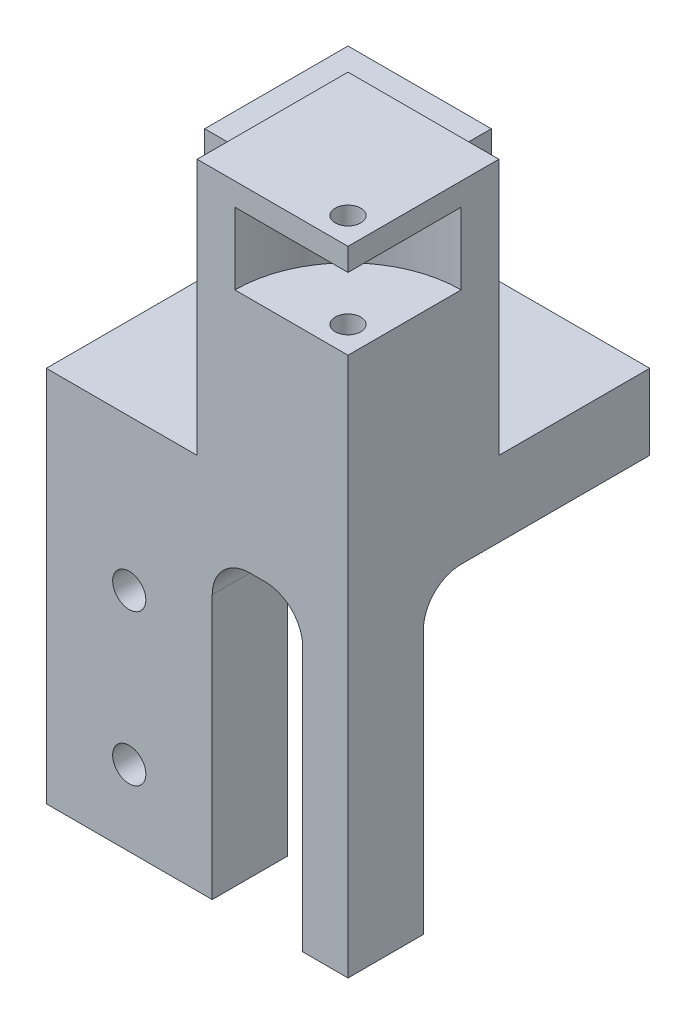
SolidWorks part; units mm, degrees
ref_plane "Front Plane" through (0, 0, 0) normal (0, 0, 1) x (1, 0, 0)
ref_plane "Top Plane" through (0, 0, 0) normal (0, 1, 0) x (1, 0, 0)
ref_plane "Right Plane" through (0, 0, 0) normal (1, 0, 0) x (0, 0, -1)
sketch "Sketch1" plane through (0, 0, 0) normal (0, 0, 1) x (1, 0, 0)
  line L0 (22, 0) -> (-22, 0) construction
  line L1 (-6.3654, 0) -> (33.6346, 0)
  line L2 (-6.3654, 0) -> (-6.3654, -50)
  line L3 (-6.3654, -50) -> (33.6346, -50)
  line L4 (33.6346, 0) -> (33.6346, -50)
  line L5 (13.6346, -50) -> (13.6346, 0) construction
  line L6 (-6.3654, -25) -> (33.6346, -25) construction
  point P252 (13.6346, -25)
  dimension "D1" = 50
  dimension "D2" = 40
extrude "Boss-Extrude1" add sketch "Sketch1" along normal blind 10
sketch "Sketch2" plane through (0, 0, 0) normal (0, 0, 1) x (1, 0, 0)
  line L0 (33.6346, 0) -> (-6.3654, 0) construction
  line L1 (33.6346, 0) -> (-6.3654, 0)
  line L2 (33.6346, 0) -> (33.6346, -10)
  line L3 (33.6346, -10) -> (-6.3654, -10)
  line L4 (-6.3654, 0) -> (-6.3654, -10)
  line L5 (13.6346, -10) -> (13.6346, 0) construction
  line L6 (33.6346, -5) -> (-6.3654, -5) construction
  line L7 (-6.3654, 0) -> (-6.3654, -50) construction
  line L8 (33.6346, -50) -> (33.6346, 0) construction
  point P164 (13.6346, -5)
  dimension "D1" = 10
extrude "Boss-Extrude2" add sketch "Sketch2" against normal blind 30
sketch "Sketch3" plane through (0, 0, 0) normal (0, 1, 0) x (1, 0, 0)
  line L0 (33.6346, -10) -> (33.6346, 30) construction
  line L1 (33.6346, -10) -> (13.6346, -10)
  line L2 (33.6346, -10) -> (33.6346, 10)
  line L3 (33.6346, 10) -> (13.6346, 10)
  line L4 (13.6346, -10) -> (13.6346, 10)
  line L9 (33.6346, -10) -> (-6.3654, -10) construction
  dimension "D1" = 20
  dimension "D2" = 20
extrude "Boss-Extrude3" add sketch "Sketch3" along normal blind 34
sketch "Sketch4" plane through (0, 0, 0) normal (0, 1, 0) x (1, 0, 0)
  line L0 (-974.1415, 10) -> (49025.8585, 10) construction
  line L1 (33.6346, 10) -> (13.6346, 10) construction
  line L8 (-6.3654, 30) -> (12.6346, 30)
  line L14 (-6.3654, 30) -> (-6.3654, 11)
  line L15 (-6.3654, 11) -> (12.6346, 11)
  line L16 (12.6346, 30) -> (12.6346, 11)
  line L17 (3.1346, 11) -> (3.1346, 30) construction
  line L18 (-6.3654, 20.5) -> (12.6346, 20.5) construction
  point P5 (23.6346, 10)
  point P165 (3.1346, 20.5)
  dimension "D1" = 19
  dimension "D2" = 19
  dimension "D3" = 19
extrude "Boss-Extrude4" add sketch "Sketch4" along normal blind 17
ref_plane "Plane2" through (0, 31, 0) normal (0, 1, 0) x (1, 0, 0)
sketch "Sketch6" plane through (0, 31, 0) normal (0, 1, 0) x (1, 0, 0)
  line L1 (13.6346, -10) -> (33.6346, -10) construction
  line L2 (33.6346, -10) -> (33.6346, 10) construction
  line L3 (33.6346, 5) -> (33.6346, -10)
  line L4 (33.6346, -10) -> (18.6346, -10)
  arc A1 (18.6346, -10) -> (33.6346, 5) centre (33.6346, -10) cw
  dimension "D1" = 15
extrude "Cut-Extrude4" cut sketch "Sketch6" against normal blind 9.5
ref_plane "Plane3" through (0, 15, 0) normal (0, 1, 0) x (1, 0, 0)
sketch "Sketch7" plane through (0, 15, 0) normal (0, 1, 0) x (1, 0, 0)
  line L0 (-2.3654, 11) -> (12.6346, 11)
  line L1 (12.6346, 11) -> (12.6346, 26)
  line L6 (12.6346, 11) -> (12.6346, 30) construction
  line L9 (-6.3654, 11) -> (12.6346, 11) construction
  arc A2 (-2.3654, 11) -> (12.6346, 26) centre (12.6346, 11) cw
  dimension "D2" = 15
extrude "Cut-Extrude13" cut sketch "Sketch7" against normal blind 9.5
sketch "Sketch8" plane through (0, 17, 0) normal (0, 1, 0) x (1, 0, 0)
  line L0 (-6.3654, 11) -> (12.6346, 11) construction
  line L1 (-6.3654, 30) -> (12.6346, 30)
  line L2 (-6.3654, 30) -> (-6.3654, 11)
  line L3 (-6.3654, 11) -> (12.6346, 11)
  line L4 (12.6346, 30) -> (12.6346, 11)
  line L5 (3.1346, 11) -> (3.1346, 30) construction
  line L6 (-6.3654, 20.5) -> (12.6346, 20.5) construction
  point P160 (3.1346, 20.5)
sketch "Sketch10" plane through (0, 31, 0) normal (0, -1, 0) x (-1, 0, 0)
  line L0 (-740.7414, -717.1068) -> (34614.5977, 34638.2323) construction
  circle A0 centre (-30.0991, -6.4645) radius 1.7
  point P2 (0, 0)
  dimension "D1" = 3.4
  dimension "D2" = 5
extrude "Cut-Extrude7" cut sketch "Sketch10" along normal through all and the other way blind 3
sketch "Sketch12" plane through (0, 0, 10) normal (0, 0, 1) x (1, 0, 0)
  line L0 (-6.3654, -50) -> (33.6346, -50) construction
  line L1 (27.6346, -50) -> (15.6346, -50)
  line L2 (27.6346, -50) -> (27.6346, -10)
  line L3 (27.6346, -10) -> (15.6346, -10)
  line L4 (15.6346, -50) -> (15.6346, -10)
  line L5 (21.6346, -10) -> (21.6346, -50) construction
  line L6 (27.6346, -30) -> (15.6346, -30) construction
  line L10 (33.6346, -50) -> (33.6346, 21.5) construction
  point P8 (33.6346, -14.25)
  point P344 (21.6346, -30)
  dimension "D1" = 12
  dimension "D2" = 40
  dimension "D3" = 6
extrude "Cut-Extrude9" cut sketch "Sketch12" against normal up to next
fillet "Fillet2" radius 5 4 edges at (15.6346, -10, 5) (27.6346, -10, 5) (4.6346, -10, 0) (30.6346, -10, 0)
sketch "Sketch13" plane through (0, 0, 10) normal (0, 0, 1) x (1, 0, 0)
  line L0 (4.6346, -1050) -> (4.6346, 48950) construction
  line L1 (-5.3654, -50) -> (14.6346, -50) construction
  circle A0 centre (4.6346, -20) radius 2.2
  circle A1 centre (4.6346, -40) radius 2.2
  point P5 (4.6346, -50)
  dimension "D1" = 4.4
  dimension "D2" = 10
  dimension "D3" = 20
extrude "Cut-Extrude10" cut sketch "Sketch13" against normal up to next
sketch "Sketch14" plane through (0, 17, 0) normal (0, 1, 0) x (1, 0, 0)
  line L0 (-694.4722, 718.1068) -> (34660.8669, -34637.2323) construction
  circle A0 centre (9.0991, 14.5355) radius 1.7
  dimension "D1" = 3.4
  dimension "D2" = 5
extrude "Cut-Extrude14" cut sketch "Sketch14" against normal blind 20
